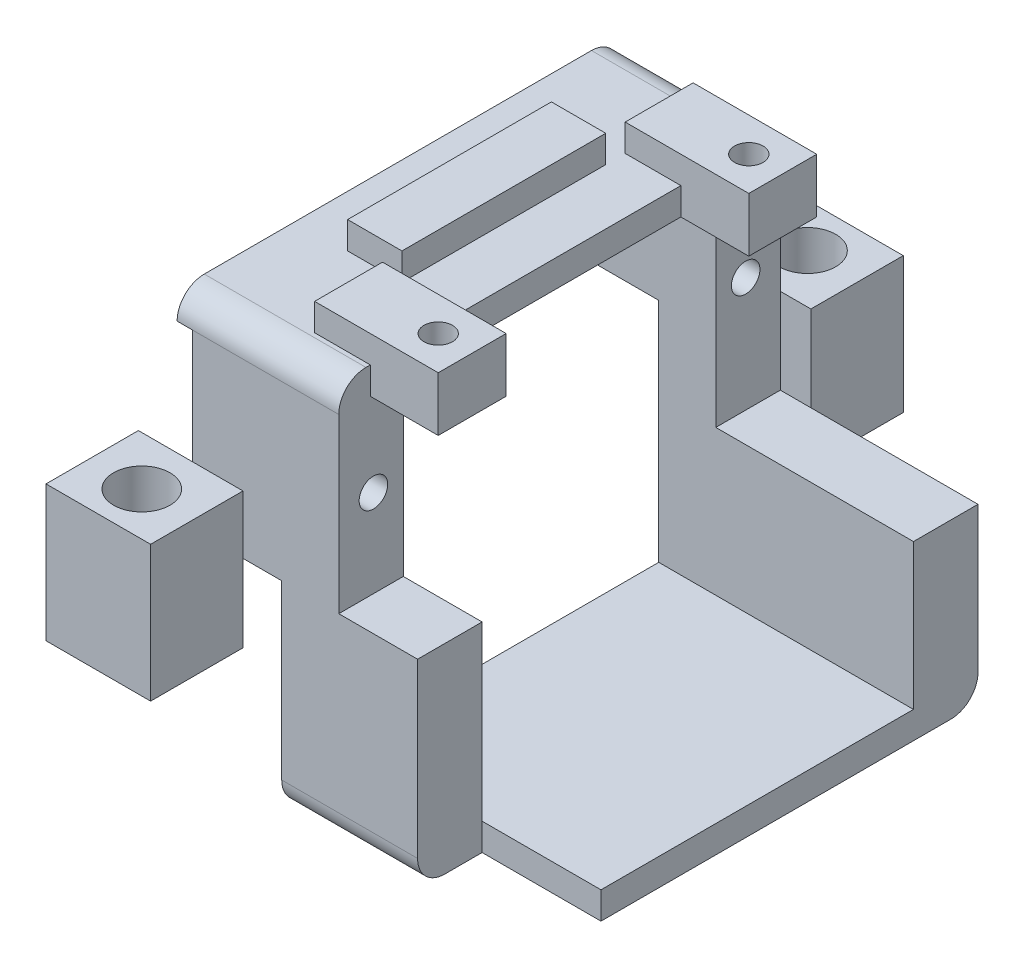
SolidWorks part; units mm, degrees
ref_plane "Front Plane" through (0, 0, 0) normal (0, 0, 1) x (1, 0, 0)
ref_plane "Top Plane" through (0, 0, 0) normal (0, 1, 0) x (1, 0, 0)
ref_plane "Right Plane" through (0, 0, 0) normal (1, 0, 0) x (0, 0, -1)
sketch "Sketch1" plane through (0, 0, 0) normal (0, 1, 0) x (1, 0, 0)
  line L0 (-1.1, 16.25) -> (-1.1, 11.5)
  line L1 (-17.65, -16.25) -> (17.65, -16.25)
  line L2 (-17.65, -16.25) -> (-17.65, 16.25)
  line L3 (-17.65, 16.25) -> (17.65, 16.25)
  line L4 (17.65, -16.25) -> (17.65, 16.25)
  line L5 (-17.65, -16.25) -> (17.65, 16.25) construction
  line L6 (-17.65, 16.25) -> (17.65, -16.25) construction
  line L7 (-1.1, 11.5) -> (17.65, 11.5)
  line L8 (-1.1, -16.25) -> (-1.1, -11.5)
  line L9 (-1.1, -11.5) -> (17.65, -11.5)
  line L10 (-1.1, 11.5) -> (-1.1, -11.5) construction
  line L11 (8.9, -11.5) -> (8.9, -16.25)
  line L12 (-8.8, 16.25) -> (-8.8, 11.5)
  line L13 (-8.8, 11.5) -> (-3.8, 11.5)
  line L14 (-3.8, 11.5) -> (-3.8, 16.25)
  line L15 (-3.8, -16.25) -> (-3.8, -11.5)
  line L16 (-3.8, -11.5) -> (-8.8, -11.5)
  line L17 (-8.8, -11.5) -> (-8.8, -16.25)
  line L18 (-8.8, 11.5) -> (-8.8, -11.5)
  line L19 (5.35, 16.25) -> (5.35, 23.05)
  line L20 (5.35, 23.05) -> (-2.35, 23.05)
  line L21 (-2.35, 23.05) -> (-2.35, 16.25)
  line L22 (-11.65, -16.25) -> (-11.65, -23.05)
  line L23 (-11.65, -23.05) -> (-3.95, -23.05)
  line L24 (-3.95, -23.05) -> (-3.95, -16.25)
  line L25 (9.53, -16.25) -> (9.53, -23.05)
  line L26 (9.53, -23.05) -> (17.23, -23.05)
  line L27 (17.23, -23.05) -> (17.23, -16.25)
  line L28 (-1.1, 11.5) -> (-1.1, -11.5)
  circle A0 centre (1.5, 19.85) radius 2.075
  circle A1 centre (13.38, -19.85) radius 2.075
  circle A2 centre (-7.8, -19.85) radius 2.075
  point P0 (0, 0)
  point P11 (-1.1, 0)
  point P31 (1.5, 23.05)
  point P45 (-7.8, -23.05)
  point P48 (13.38, -23.05)
  dimension "D11" = 4.15
  dimension "D18" = 4.15
  dimension "D19" = 4.15
  dimension "D1" = 32.5
  dimension "D2" = 23
  dimension "D3" = 8.75
  dimension "D4" = 10
  dimension "D5" = 16.55
  dimension "D6" = 2.7
  dimension "D7" = 5
  dimension "D8" = 1.5
  dimension "D9" = 7.7
  dimension "D10" = 6.8
  dimension "D12" = 9.85
  dimension "D13" = 31.03
  dimension "D14" = 7.7
  dimension "D15" = 19.85
  dimension "D16" = 7.7
  dimension "D17" = 6.8
  dimension "D20" = 19.85
extrude "Boss-Extrude1" add sketch "Sketch1" against normal blind 2 contours L7 L28 L9 L4 | L0 L7 L4 L3 | L11 L9 L8 L1 region at (8.275, 0, -13.875) region at (8.275, 0, 0) region at (3.9, 0, 13.875)
extrude "Boss-Extrude2" add sketch "Sketch1<3>" along normal blind 12.7 contours L0 L7 L4 L3 | L11 L9 L8 L1 region at (8.275, 0, -13.875) region at (3.9, 0, 13.875)
sketch "Sketch1<3>" plane through (0, 0, 0) normal (0, 1, 0) x (1, 0, 0) same geometry as "Sketch1"
sketch "Sketch3" plane through (0, 0, 0) normal (0, 1, 0) x (1, 0, 0)
  line L0 (3.1, 16.25) -> (3.1, 11.5)
  line L1 (-17.65, 16.25) -> (17.65, 16.25) construction
  line L2 (-1.1, 11.5) -> (17.65, 11.5) construction
  line L3 (3.1, 11.5) -> (-17.65, 11.5)
  line L4 (-17.65, -16.25) -> (-17.65, 16.25) construction
  line L5 (3.1, -16.25) -> (3.1, -11.5)
  line L6 (-17.65, -16.25) -> (17.65, -16.25) construction
  line L7 (-1.1, -11.5) -> (17.65, -11.5) construction
  line L8 (3.1, -11.5) -> (-17.65, -11.5)
  line L9 (3.1, 11.5) -> (3.1, -11.5)
  line L10 (-7.65, -11.5) -> (-7.65, -16.275)
  line L11 (3.1, 16.25) -> (-17.65, 16.25)
  line L12 (-17.65, 16.25) -> (-17.65, 11.5)
  line L13 (-17.65, -11.5) -> (-17.65, -16.25)
  line L14 (-17.65, -16.25) -> (3.1, -16.25)
  line L15 (-8.8, 11.5) -> (-8.8, -11.5)
  line L16 (-8.8, 11.5) -> (-8.8, 16.25)
  line L17 (-8.8, -11.5) -> (-8.8, -16.25)
  dimension "D1" = 20.75
  dimension "D2" = 10
extrude "Boss-Extrude3" add sketch "Sketch3" along normal blind 12.7 from surface contours L11 L12 L3 L0 | L10 L14 L5 L8 region at (-2.85, 0, -13.875) region at (-2.275, 0, 13.875) starting at face at (8.275, 12.7, -13.875)
extrude "Boss-Extrude4" add sketch "Sketch3<3>" along normal blind 2 from surface contours L16 L3 L0 L11 | L3 L15 L8 L9 | L10 L14 L5 L8 | L8 L17 L14 L10 region at (-2.85, 0, -13.875) region at (-2.85, 0, 0) region at (-2.275, 0, 13.875) region at (-8.225, 0, 13.875) starting at face at (-2.275, 25.4, 13.875)
sketch "Sketch3<3>" plane through (0, 0, 0) normal (0, 1, 0) x (1, 0, 0) same geometry as "Sketch3"
sketch "Sketch2" plane through (0, 0, 0) normal (1, 0, 0) x (0, 0, -1)
  line L0 (13.7, 6.45) -> (-13.7, 6.45) construction
  line L1 (-13.7, 19.15) -> (13.7, 19.15) construction
  circle A0 centre (13.7, 6.45) radius 1.05
  circle A1 centre (-13.7, 6.45) radius 1.05
  circle A2 centre (-13.7, 19.15) radius 1.05
  circle A3 centre (13.7, 19.15) radius 1.05
  point P4 (0, 6.45)
  dimension "D1" = 2.1
  dimension "D2" = 2.1
  dimension "D6" = 2.1
  dimension "D7" = 2.1
  dimension "D3" = 27.4
  dimension "D4" = 6.45
  dimension "D5" = 6.45
extrude "Cut-Extrude1" cut sketch "Sketch2" along normal blind 8 from surface contours A1 | A0 region at (0, 6.45, -13.7) region at (0, 6.45, 13.7) starting at face at (-1.1, 5.85, 0)
extrude "Cut-Extrude2" cut sketch "Sketch2<3>" against normal blind 8 from surface contours A3 | A2 region at (0, 19.15, 13.7) region at (0, 19.15, -13.7) starting at face at (3.1, 19.55, 0)
sketch "Sketch2<3>" plane through (0, 0, 0) normal (1, 0, 0) x (0, 0, -1) same geometry as "Sketch2"
extrude "Boss-Extrude5" add sketch "Sketch1<4>" along normal blind 10 from offset 7 contours L20 L21 L3 L19 A0 | L23 L24 L1 L22 A2 region at (-1.725, 0, -16.3527) region at (-4.0527, 0, 19.65)
sketch "Sketch1<4>" plane through (0, 0, 0) normal (0, 1, 0) x (1, 0, 0) same geometry as "Sketch1"
fillet "Fillet1" radius 2 4 edges at (3.9, -2, 16.25) (-2.85, 27.4, 16.25) (8.275, -2, -16.25) (-2.85, 27.4, -16.25)
sketch "Sketch5" plane through (0, 0, 0) normal (0, 1, 0) x (1, 0, 0)
  line L1 (17.65, 16.25) -> (3.1, 16.25)
  line L2 (17.65, 16.25) -> (17.65, 11.5)
  line L3 (17.65, 11.5) -> (3.1, 11.5)
  line L4 (3.1, 16.25) -> (3.1, 11.5)
extrude "Cut-Extrude3" cut sketch "Sketch5" against normal blind 2 from surface starting at face at (9.37, 12.7, -14.35)
sketch "Sketch6" plane through (0, 0, 0) normal (0, 1, 0) x (1, 0, 0)
  line L1 (-8.8, 11.5) -> (-1.1, 11.5)
  line L2 (-8.8, 11.5) -> (-8.8, 16.25)
  line L3 (-8.8, 16.25) -> (-1.1, 16.25)
  line L4 (-1.1, 11.5) -> (-1.1, 16.25)
extrude "Cut-Extrude4" cut sketch "Sketch6" along normal blind 4 from surface starting at face at (-4.43, 12.7, -14.35)
sketch "Sketch7" plane through (0, 0, 0) normal (0, 1, 0) x (1, 0, 0)
  line L0 (5.6, 11.43) -> (5.6, -11.43) construction
  line L2 (3.1, 8.93) -> (8.1, 8.93)
  line L3 (3.1, 8.93) -> (3.1, 13.93)
  line L4 (3.1, 13.93) -> (8.1, 13.93)
  line L5 (8.1, 8.93) -> (8.1, 13.93)
  line L6 (3.1, 8.93) -> (8.1, 13.93) construction
  line L7 (3.1, 13.93) -> (8.1, 8.93) construction
  line L8 (-5, -7.5) -> (-1, -7.5)
  line L9 (3.1, -8.93) -> (8.1, -8.93)
  line L10 (3.1, -8.93) -> (3.1, -13.93)
  line L11 (3.1, -13.93) -> (8.1, -13.93)
  line L12 (8.1, -8.93) -> (8.1, -13.93)
  line L13 (3.1, -8.93) -> (8.1, -13.93) construction
  line L14 (3.1, -13.93) -> (8.1, -8.93) construction
  line L15 (-5, -7.5) -> (-5, 7.5)
  line L16 (3.1, 12.65) -> (3.1, 14.75) construction
  line L17 (-5, 7.5) -> (-1, 7.5)
  line L18 (-1, -7.5) -> (-1, 7.5)
  line L19 (-5, -7.5) -> (-1, 7.5) construction
  line L20 (-5, 7.5) -> (-1, -7.5) construction
  line L22 (3.1, -8.93) -> (-1, -8.93)
  line L23 (3.1, -8.93) -> (3.1, -13.93)
  line L24 (3.1, -13.93) -> (-1, -13.93)
  line L25 (-1, -8.93) -> (-1, -13.93)
  line L26 (3.1, 13.93) -> (-1, 13.93)
  line L27 (3.1, 13.93) -> (3.1, 8.93)
  line L28 (3.1, 8.93) -> (-1, 8.93)
  line L29 (-1, 13.93) -> (-1, 8.93)
  circle A0 centre (5.6, 11.43) radius 1.05
  circle A1 centre (5.6, -11.43) radius 1.05
  point P4 (5.6, 0)
  point P14 (-3, 0)
  dimension "D2" = 2.1
  dimension "D3" = 2.1
  dimension "D1" = 22.86
  dimension "D4" = 4
  dimension "D5" = 5
  dimension "D6" = 5
  dimension "D7" = 5
  dimension "D8" = 5
  dimension "D9" = 15
  dimension "D10" = 3
extrude "Boss-Extrude6" add sketch "Sketch7" along normal blind 2 and the other way blind 2 from surface contours L8 L18 L17 L15 | L26 L29 L18 L28 L3 | L2 L5 L4 L3 A0 | L18 L25 L24 L10 L22 | L12 L9 L10 L11 A1 region at (3.1707, 0, -11.43) region at (1.05, 0, -11.43) region at (-3, 0, 0) region at (5.6, 0, 9.0007) region at (1.05, 0, 11.43) starting at face at (-2.85, 27.4, 0)
